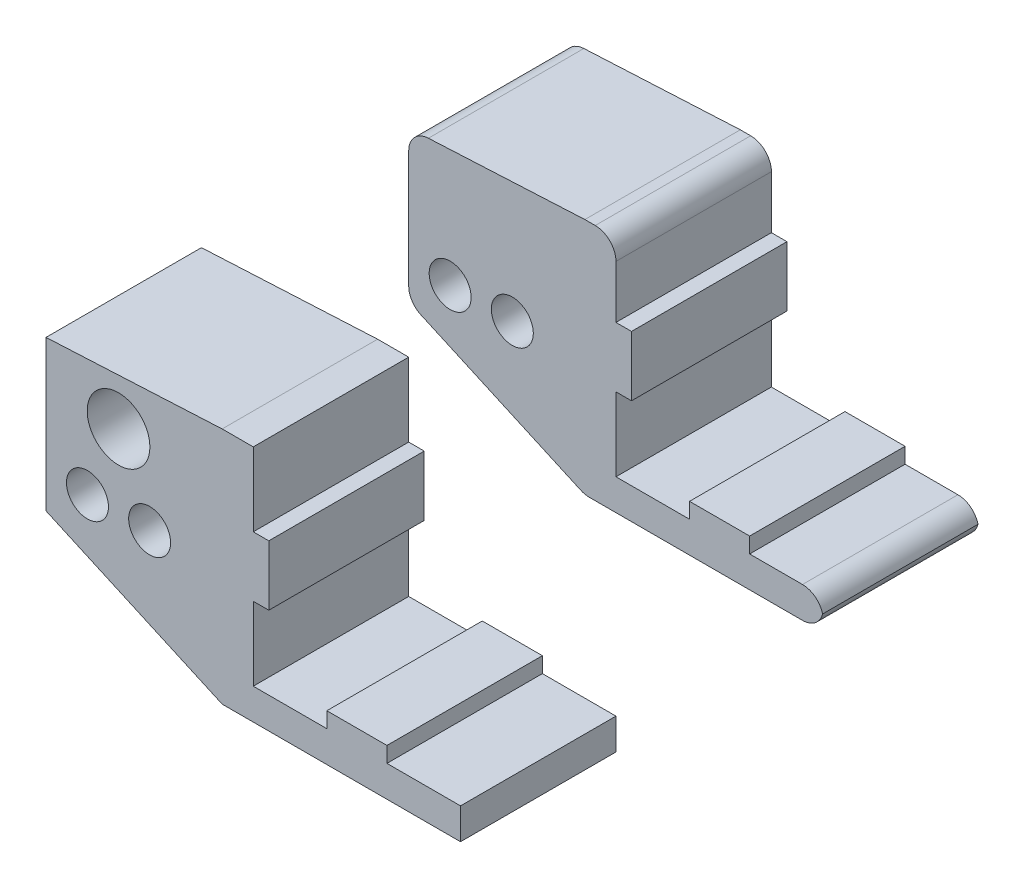
SolidWorks part; units mm, degrees
ref_plane "Front Plane" through (0, 0, 0) normal (0, 0, 1) x (1, 0, 0)
ref_plane "Top Plane" through (0, 0, 0) normal (0, 1, 0) x (1, 0, 0)
ref_plane "Right Plane" through (0, 0, 0) normal (1, 0, 0) x (0, 0, -1)
sketch "Sketch1" plane through (0, 0, 0) normal (0, 0, 1) x (1, 0, 0)
  line L0 (53.4899, -84.3159) -> (59.4899, -84.3159) construction
  line L1 (56.4899, -84.3159) -> (66.4899, -84.3159) construction
  line L2 (66.4899, -72.3159) -> (69.4899, -72.3159)
  line L3 (56.4899, -77.3159) -> (56.4899, -84.3159) construction
  line L4 (49.4899, -73.1659) -> (49.4899, -87.6659)
  line L7 (66.4899, -95.3159) -> (89.4899, -95.3159)
  line L9 (69.4899, -72.3159) -> (69.4899, -79.4159)
  line L10 (69.4899, -92.3159) -> (76.5899, -92.3159)
  line L11 (89.4899, -92.3159) -> (89.4899, -95.3159)
  line L14 (49.4899, -87.6659) -> (66.4899, -95.3159)
  line L17 (56.4899, -77.3159) -> (66.4899, -77.3159) construction
  line L18 (66.4899, -72.3159) -> (49.4899, -73.1659)
  line L19 (56.4899, -84.3159) -> (56.4899, -90.8159) construction
  line L20 (56.4899, -84.3159) -> (49.4899, -84.3159) construction
  line L21 (56.4899, -84.3159) -> (56.4899, -72.8159) construction
  line L22 (66.4899, -77.3159) -> (66.4899, -95.3159) construction
  line L23 (89.4899, 311.6195) -> (89.4899, -198.3805) construction
  line L24 (79.4899, -90.8159) -> (79.4899, -92.3159) construction
  line L26 (76.5899, -92.3159) -> (76.5899, -90.8159)
  line L27 (76.5899, -90.8159) -> (82.3899, -90.8159)
  line L28 (82.3899, -92.3159) -> (82.3899, -90.8159)
  line L29 (69.4899, -85.2159) -> (70.9899, -85.2159)
  line L31 (69.4899, -79.4159) -> (70.9899, -79.4159)
  line L32 (70.9899, -85.2159) -> (70.9899, -79.4159)
  line L33 (69.4899, -82.3159) -> (70.9899, -82.3159) construction
  line L34 (82.3899, -92.3159) -> (89.4899, -92.3159)
  line L35 (69.4899, -85.2159) -> (69.4899, -92.3159)
  circle A0 centre (56.4899, -77.3159) radius 3.025
  circle A1 centre (53.4899, -84.3159) radius 2.025
  circle A2 centre (59.4899, -84.3159) radius 2.025
  dimension "D3" = 4.05
  dimension "D4" = 6.05
  dimension "D1" = 3
  dimension "D2" = 6
  dimension "D5" = 6.5
  dimension "D6" = 7
  dimension "D7" = 11.5
  dimension "D8" = 23
  dimension "D9" = 17
  dimension "D10" = 20
  dimension "D11" = 20
  dimension "D12" = 8
  dimension "D13" = 5.8
  dimension "D14" = 1.5
extrude "Boss-Extrude1" add sketch "Sketch1" along normal blind 15
extrude "Boss-Extrude2" add sketch "Sketch1<2>" along normal up to surface (15 mm away) from offset 6 contours A0 region at (56.4899, -77.3159, 0) up to face at (55.5149, -84.3159, 15)
sketch "Sketch1<2>" plane through (0, 0, 0) normal (0, 0, 1) x (1, 0, 0) same geometry as "Sketch1"
sketch "Sketch2" plane through (0, -95.3159, 0) normal (0, -1, 0) x (1, 0, 0)
  line L0 (89.4899, 0) -> (69.4899, 15) construction
  line L1 (66.4899, 15) -> (89.4899, 15) construction
  line L2 (69.4899, 15) -> (89.4899, 15) construction
  circle A0 centre (79.4899, 7.5) radius 2.65
  dimension "D2" = 5.3
  dimension "D1" = 20
extrude "Cut-Extrude1" cut sketch "Sketch2" against normal up to surface (3 mm away) up to face at (73.0399, -92.3159, 7.5)
ref_plane "Plane1" through (0, 0, 25) normal (0, 0, 1) x (1, 0, 0)
mirror "Mirror4" about plane through (0, 0, 25) normal (0, 0, 1) of bodies 103
fillet "Fillet1" radius 2 6 edges at (89.4899, -95.3159, 7.5) (89.4899, -92.3159, 7.5) (66.4899, -95.3159, 7.5) (49.4899, -87.6659, 7.5) (49.4899, -73.1659, 7.5) (69.4899, -72.3159, 7.5)
